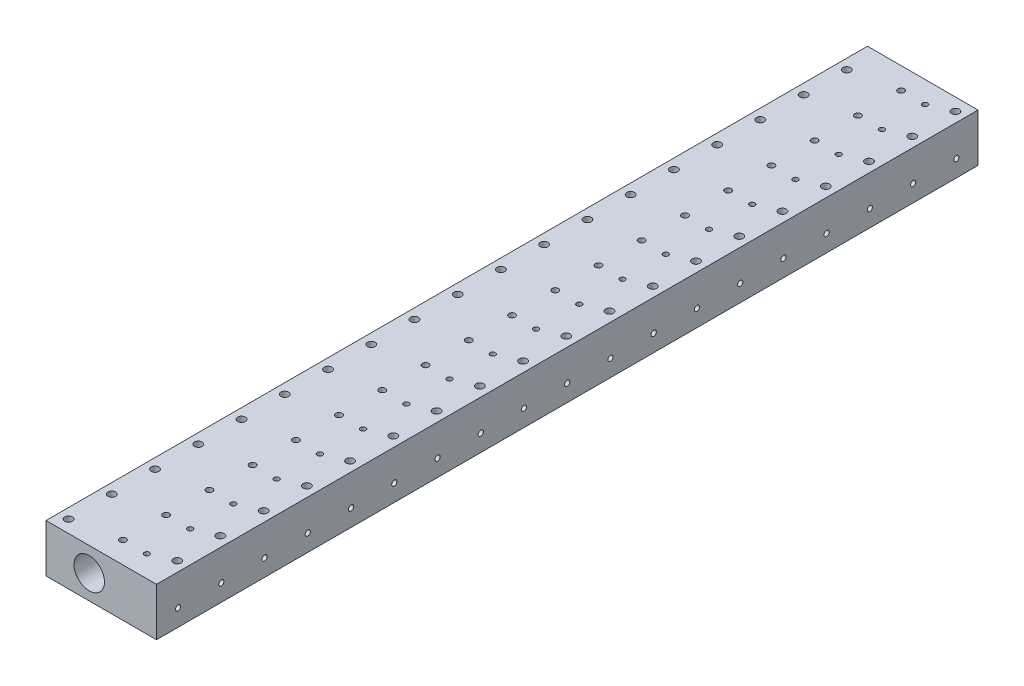
SolidWorks part; units mm, degrees
ref_plane "Front Plane" through (0, 0, 0) normal (0, 0, 1) x (1, 0, 0)
ref_plane "Top Plane" through (0, 0, 0) normal (0, 1, 0) x (1, 0, 0)
ref_plane "Right Plane" through (0, 0, 0) normal (1, 0, 0) x (0, 0, -1)
sketch "Sketch1" plane through (0, 0, 0) normal (0, 0, 1) x (1, 0, 0)
  line L1 (-11.5, -5) -> (11.5, -5)
  line L2 (-11.5, -5) -> (-11.5, 5)
  line L3 (-11.5, 5) -> (11.5, 5)
  line L4 (11.5, -5) -> (11.5, 5)
  line L5 (-11.5, -5) -> (11.5, 5) construction
  line L6 (-11.5, 5) -> (11.5, -5) construction
  point P0 (0, 0)
  dimension "D1" = 23
  dimension "D2" = 10
extrude "Boss-Extrude1" add sketch "Sketch1" against normal blind 171
hole_wizard "#55 (0.052) Diameter Hole1" positions "Sketch2" profile "Sketch4" hole size "#55" standard "ANSI Inch"
sketch "Sketch2" plane through (0, 5, 0) normal (0, 1, 0) x (1, 0, 0)
  line L0 (11.5, 0) -> (-11.5, 0) construction
  point P0 (0, 4.5)
  dimension "D1" = 4.5
sketch "Sketch4" plane through (0, 5, -4.5) normal (1, 0, 0) x (0, 0, 1)
  line L0 (0, 0) -> (0, 7.3968)
  line L1 (0, 7.3968) -> (0.6604, 7)
  line L2 (0.6604, 7) -> (0.6604, 0)
  line L5 (0.6604, 0) -> (0, 0)
  line L10 (0, 7.3968) -> (-0.6604, 7) construction
  line L11 (0, -6.35) -> (0, 107.95) construction
  dimension "Hole Dia." = 1.3208
  dimension "Hole Depth" = 7
  dimension "Drill Angle" = 118
sketch "Sketch5" plane through (0, 0, 0) normal (0, 0, 1) x (1, 0, 0)
  circle A0 centre (-2.5, 0) radius 3.175
  dimension "D2" = 6.35
  dimension "D1" = 2.5
extrude "Cut-Extrude1" cut sketch "Sketch5" against normal through all
hole_wizard "M2x0.4 Tapped Hole1" positions "Sketch6" profile "Sketch8" tap size "M2x0.4" standard "ANSI Metric"
sketch "Sketch6" plane through (0, 5, 0) normal (0, 1, 0) x (1, 0, 0)
  line L0 (0, 4.5) -> (5, 4.5) construction
  point P0 (9.4, 6.4)
  point P2 (-9.4, 2.6)
  dimension "D1" = 9.4
  dimension "D2" = 9.4
  dimension "D3" = 1.9
  dimension "D4" = 1.9
sketch "Sketch8" plane through (9.4, 5, -6.4) normal (1, 0, 0) x (0, 0, 1)
  line L0 (0, 0) -> (0, 5.6807)
  line L1 (0, 5.6807) -> (0.8, 5.2)
  line L2 (0.8, 5.2) -> (0.8, 0)
  line L5 (0.8, 0) -> (0, 0)
  line L10 (0, 5.6807) -> (-0.8, 5.2) construction
  line L11 (0, -6.35) -> (0, 107.95) construction
  dimension "Tap Drill Dia." = 1.6
  dimension "Tap Drill Depth" = 5.2
  dimension "Drill Angle" = 118
cosmetic thread "Hole Thread1" parameters "D1"=4, "D2"=2
cosmetic thread "Hole Thread2" parameters "D1"=4, "D2"=2
hole_wizard "#57 (0.043) Diameter Hole2" positions "Sketch11" profile "Sketch12" hole size "#57" standard "ANSI Inch"
sketch "Sketch11" plane through (11.5, 0, 0) normal (1, 0, 0) x (0, 0, -1)
  line L0 (0, -5) -> (0, 5) construction
  line L1 (171, 5) -> (0, 5) construction
  point P0 (4.5, -1.5)
  dimension "D1" = 4.5
  dimension "D2" = 6.5
sketch "Sketch12" plane through (11.5, -1.5, -4.5) normal (0, 1, 0) x (0, 0, -1)
  line L0 (0, 0) -> (0, 6.3281)
  line L1 (0, 6.3281) -> (0.5461, 6)
  line L2 (0.5461, 6) -> (0.5461, 0)
  line L5 (0.5461, 0) -> (0, 0)
  line L10 (0, 6.3281) -> (-0.5461, 6) construction
  line L11 (0, -6.35) -> (0, 107.95) construction
  dimension "Hole Dia." = 1.0922
  dimension "Hole Depth" = 6
  dimension "Drill Angle" = 118
hole_wizard "#57 (0.043) Diameter Hole1" positions "Sketch13" profile "Sketch14" hole size "#57" standard "ANSI Inch"
sketch "Sketch13" plane through (0, 5, 0) normal (0, 1, 0) x (1, 0, 0)
  line L0 (0, 4.5) -> (5, 4.5)
  point P0 (5, 4.5)
  dimension "D1" = 5
sketch "Sketch14" plane through (5, 5, -4.5) normal (1, 0, 0) x (0, 0, 1)
  line L0 (0, 0) -> (0, 7.8281)
  line L1 (0, 7.8281) -> (0.5461, 7.5)
  line L2 (0.5461, 7.5) -> (0.5461, 0)
  line L5 (0.5461, 0) -> (0, 0)
  line L10 (0, 7.8281) -> (-0.5461, 7.5) construction
  line L11 (0, -6.35) -> (0, 107.95) construction
  dimension "Hole Dia." = 1.0922
  dimension "Hole Depth" = 7.5
  dimension "Drill Angle" = 118
pattern_linear "LPattern1" count 19 spacing 9 along (0, 0, -1) of "#55 (0.052) Diameter Hole1", "M2x0.4 Tapped Hole1", "#57 (0.043) Diameter Hole2", "#57 (0.043) Diameter Hole1"
